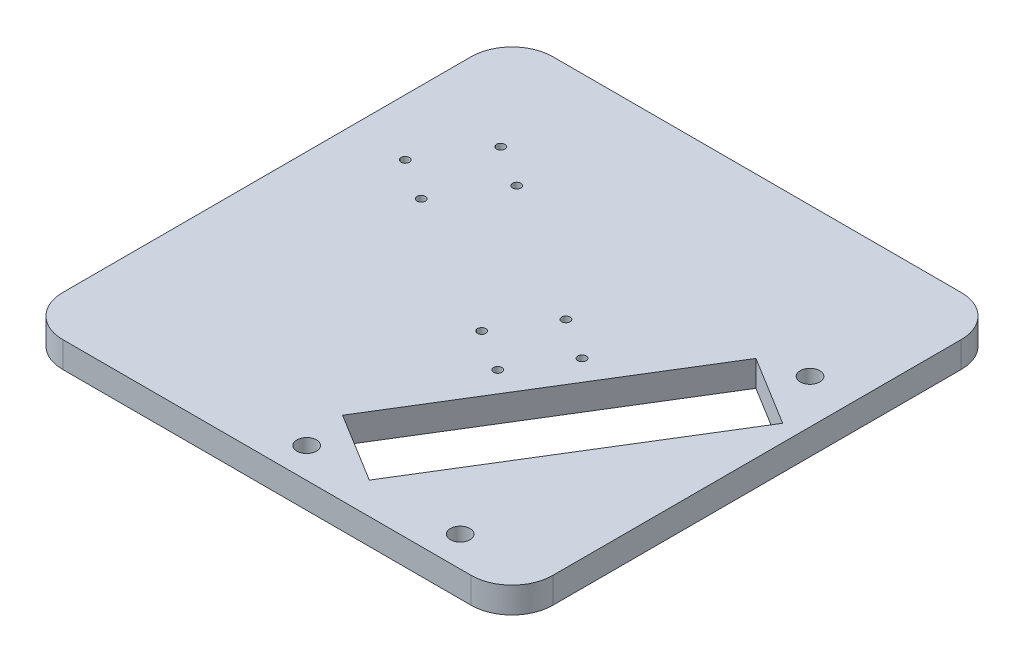
SolidWorks part; units mm, degrees
ref_plane "Front Plane" through (0, 0, 0) normal (0, 0, 1) x (1, 0, 0)
ref_plane "Top Plane" through (0, 0, 0) normal (0, 1, 0) x (1, 0, 0)
ref_plane "Right Plane" through (0, 0, 0) normal (1, 0, 0) x (0, 0, -1)
sketch "Sketch1" plane through (0, 0, 0) normal (0, 1, 0) x (1, 0, 0)
  line L1 (10, 0) -> (110, 0)
  line L2 (0, 10) -> (0, 110)
  line L3 (10, 120) -> (110, 120)
  line L4 (120, 10) -> (120, 110)
  arc A0 (110, 0) -> (120, 10) centre (110, 10) ccw
  arc A1 (10, 0) -> (0, 10) centre (10, 10) cw
  arc A2 (0, 110) -> (10, 120) centre (10, 110) cw
  arc A3 (110, 120) -> (120, 110) centre (110, 110) cw
  point P7 (120, 0)
  point P10 (0, 0)
  point P13 (0, 120)
  point P16 (120, 120)
  dimension "D3" = 10
  dimension "D1" = 120
  dimension "D2" = 120
extrude "Boss-Extrude1" add sketch "Sketch1" along normal blind 6.35
sketch "Sketch2" plane through (0, 6.35, 0) normal (0, 1, 0) x (1, 0, 0)
  line L0 (58.0317, 5) -> (102.0317, 5) construction
  line L1 (102.0317, 5) -> (113, 94.33) construction
  line L2 (113, 94.33) -> (58.0317, 5) construction
  line L5 (60.2915, 18.2132) -> (77.325, 7.7318)
  line L6 (77.325, 7.7318) -> (115.886, 70.398)
  line L7 (115.886, 70.398) -> (98.8525, 80.8794)
  line L8 (60.2915, 18.2132) -> (98.8525, 80.8794)
  line L9 (10, 0) -> (110, 0) construction
  line L10 (120, 10) -> (120, 110) construction
  circle A0 centre (62.3264, 7.4) radius 2.4
  circle A1 centre (99.9083, 7.4) radius 2.4
  circle A2 centre (109.2767, 83.6997) radius 2.4
  dimension "D6" = 4.8
  dimension "D7" = 4.8
  dimension "D8" = 4.8
  dimension "D1" = 97
  dimension "D2" = 44
  dimension "D3" = 89.33
  dimension "D4" = 5
  dimension "D5" = 7
  dimension "D9" = 20
  dimension "D10" = 73.58
  dimension "D11" = 5
  dimension "D12" = 7.865
  dimension "D13" = 8.1428
extrude "Cut-Extrude1" cut sketch "Sketch2" against normal through all
sketch "Sketch5" plane through (0, 6.35, 0) normal (0, 1, 0) x (1, 0, 0)
  line L0 (79.572, 49.5463) -> (0, 98.5101) construction
  line L1 (98.8525, 80.8794) -> (60.2915, 18.2132) construction
  line L2 (0, 110) -> (0, 10) construction
  circle A0 centre (69.6797, 46.8272) radius 1.025
  circle A1 centre (59.4596, 53.1161) radius 1.025
  circle A2 centre (77.5408, 59.6023) radius 1.025
  circle A3 centre (67.3207, 65.8912) radius 1.025
  circle A4 centre (13.7968, 80.0401) radius 1.025
  circle A5 centre (24.0169, 73.7513) radius 1.025
  circle A6 centre (32.9261, 88.2297) radius 1.025
  circle A7 centre (22.706, 94.5186) radius 1.025
  dimension "D2" = 2.05
  dimension "D3" = 2.05
  dimension "D4" = 2.05
  dimension "D5" = 2.05
  dimension "D14" = 2.05
  dimension "D15" = 2.05
  dimension "D16" = 2.05
  dimension "D17" = 2.05
  dimension "D1" = 90
  dimension "D6" = 7.5
  dimension "D7" = 7.5
  dimension "D8" = 7.5
  dimension "D9" = 7.5
  dimension "D10" = 7
  dimension "D11" = 7
  dimension "D12" = 12
  dimension "D13" = 12
  dimension "D18" = 8.5
  dimension "D19" = 8.5
  dimension "D20" = 8.5
  dimension "D21" = 8.5
  dimension "D22" = 60
  dimension "D23" = 60
  dimension "D24" = 12
  dimension "D25" = 12
extrude "Cut-Extrude2" cut sketch "Sketch5" against normal through all
sketch "Sketch4" plane through (0, 0, 0) normal (0, -1, 0) x (1, 0, 0)
  line L0 (79.572, -49.5463) -> (96.6055, -39.0649) construction
  line L1 (98.8525, -80.8794) -> (60.2915, -18.2132) construction
  line L2 (77.325, -7.7318) -> (115.886, -70.398) construction
